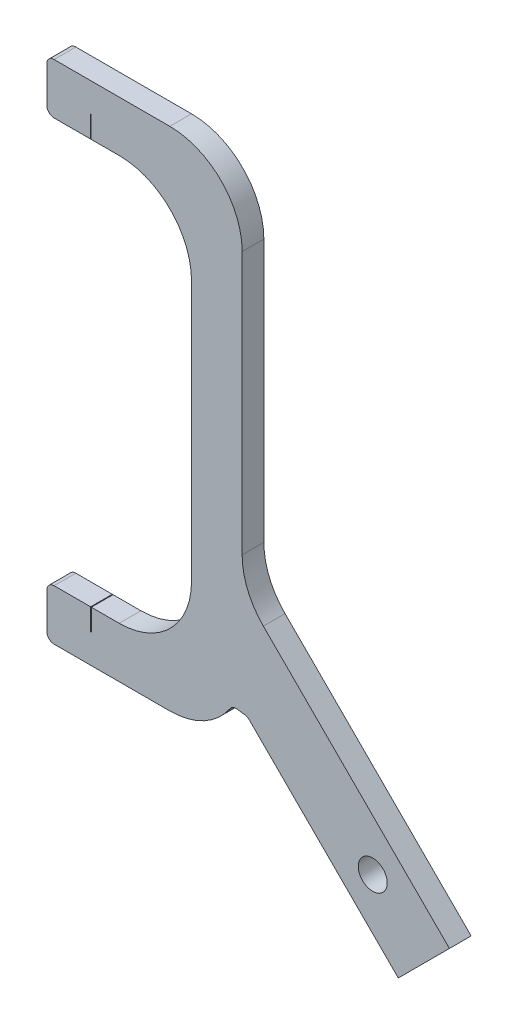
SolidWorks part; units mm, degrees
ref_plane "Front Plane" through (0, 0, 0) normal (0, 0, 1) x (1, 0, 0)
ref_plane "Top Plane" through (0, 0, 0) normal (0, 1, 0) x (1, 0, 0)
ref_plane "Right Plane" through (0, 0, 0) normal (1, 0, 0) x (0, 0, -1)
sketch "Sketch1" plane through (0, 0, 0) normal (0, 0, 1) x (1, 0, 0)
  line L0 (1, 0) -> (17, 0)
  line L1 (27, -10.0928) -> (27, -46.3053)
  line L2 (17, -70) -> (1, -70)
  line L3 (0, -69) -> (0, -64)
  line L4 (1, -63) -> (10, -63)
  line L5 (20, -53) -> (20, -17)
  line L6 (10, -7) -> (1, -7)
  line L7 (0, -6) -> (0, -1)
  line L14 (27, -10.0928) -> (27, -10)
  line L16 (25.3705, -46.8642) -> (52.661, -76.1084) construction
  line L18 (48.587, -86.1765) -> (27.9671, -65.5567)
  line L19 (48.587, -86.1765) -> (55.658, -79.1054)
  line L21 (55.658, -79.1054) -> (29.9289, -53.3763)
  line L22 (48.587, -86.1765) -> (33.8231, -52.1881) construction
  line L23 (27, -57.0782) -> (55.658, -79.1054) construction
  line L28 (26.2752, -65.1241) -> (27.3918, -65.2725)
  arc A1 (25.3122, -65.5594) -> (17, -70) centre (17, -60) cw
  arc A2 (10, -63) -> (20, -53) centre (10, -53) ccw
  arc A3 (20, -17) -> (10, -7) centre (10, -17) ccw
  arc A4 (0, -64) -> (1, -63) centre (1, -64) cw
  arc A5 (0, -69) -> (1, -70) centre (1, -69) ccw
  arc A6 (0, -1) -> (1, 0) centre (1, -1) cw
  arc A7 (0, -6) -> (1, -7) centre (1, -6) ccw
  arc A8 (17, 0) -> (27, -10) centre (17, -10) cw
  arc A9 (29.9289, -53.3763) -> (27, -46.3053) centre (37, -46.3053) cw
  arc A12 (27.3918, -65.2725) -> (27.9671, -65.5567) centre (27.26, -66.2638) cw
  arc A13 (26.2752, -65.1241) -> (25.3122, -65.5594) centre (26.1434, -66.1153) ccw
  point P10 (40.4318, -67.4022)
  point P11 (27, 0)
  point P14 (27, -70)
  point P25 (0, 0)
  point P30 (37.4955, 3.7564)
  dimension "D7" = 10
  dimension "D8" = 1
  dimension "D6" = 10
  dimension "D10" = 10
  dimension "D11" = 1
  dimension "D1" = 7
  dimension "D2" = 7
  dimension "D3" = 7
  dimension "D4" = 20
  dimension "D5" = 70
  dimension "D9" = 10
  dimension "D13" = 135
  dimension "D14" = 40
extrude "Boss-Extrude1" add sketch "Sketch1" along normal blind 3
sketch "Sketch2" plane through (0, -63, 0) normal (0, 1, 0) x (1, 0, 0)
  line L0 (27, -1.5) -> (6.1, -1.5) construction
  line L1 (27, -3) -> (27, 0) construction
  line L2 (10, 0) -> (1, 0) construction
  line L3 (6.05, -3) -> (6.15, -3)
  line L4 (6.05, -3) -> (6.05, 0)
  line L5 (6.05, 0) -> (6.15, 0)
  line L6 (6.15, -3) -> (6.15, 0)
  line L7 (6.05, -3) -> (6.15, 0) construction
  line L8 (6.05, 0) -> (6.15, -3) construction
  dimension "D2" = 0.1
extrude "Cut-Extrude1" cut sketch "Sketch2" against normal blind 3
sketch "Sketch3" plane through (0, -7, 0) normal (0, -1, 0) x (1, 0, 0)
  line L0 (27, 1.5) -> (6.05, 1.5) construction
  line L1 (27, 3) -> (27, 0) construction
  line L2 (1, 3) -> (10, 3) construction
  line L3 (6, 0) -> (6.1, 0)
  line L4 (6, 0) -> (6, 3)
  line L5 (6, 3) -> (6.1, 3)
  line L6 (6.1, 0) -> (6.1, 3)
  line L7 (6, 0) -> (6.1, 3) construction
  line L8 (6, 3) -> (6.1, 0) construction
  dimension "D2" = 0.1
extrude "Cut-Extrude2" cut sketch "Sketch3" against normal blind 3
sketch "Sketch4" plane through (0, 0, 3) normal (0, 0, 1) x (1, 0, 0)
  line L0 (52.1225, -82.641) -> (31.9288, -62.4473) construction
  line L2 (48.587, -86.1765) -> (55.658, -79.1054) construction
  circle A0 centre (45.0514, -75.5699) radius 2
  point P6 (0, 0)
  dimension "D1" = 4
  dimension "D2" = 10
extrude "Cut-Extrude3" cut sketch "Sketch4" against normal blind 10
equation "\"A.L\"= 0.07m"
equation "\"A.h\"= 0.007m"
equation "\"A.d\"= 0.003m"
equation "\"A.delta\"= 45.0001"
equation "\"A.w\"= 0.02m"
equation "\"A.v\"= 0.03m"
equation "\"A.s\"= 0.014m"
equation "\"A.t\"= 0.007m"
equation "\"B.L\"= 0.065m"
equation "\"B.h\"= 0.008m"
equation "\"B.s\"= 0.016m"
equation "\"B.t\"= 0.008m"
equation "\"C.h\"= 0.0065m"
equation "\"C.d\"= 0.003m"
equation "\"C.L\"= 0.05m"
equation "\"C.wmax\"= 0.005m"
equation "\"D.L\"= 0.06m"
equation "\"D.h\"= 0.008m"
equation "\"D.s\"= 0.012m"
equation "\"D.t\"= 0.008m"
equation "\"a_h\"= 0.0002m"
equation "\"a_d\"= 0.003m"
equation "\"a_L\"= 0.008m"
equation "\"b_h\"= 0.0004m"
equation "\"b_d\"= 0.003m"
equation "\"b_L\"= 0.007m"
equation "\"c_h\"= 0.0001m"
equation "\"c_d\"= 0.003m"
equation "\"c_L\"= 0.01m"
equation "\"d_h\"= 0.0001m"
equation "\"d_d\"= 0.003m"
equation "\"d_L\"= 0.01m"
equation "\"S.h\"= 0.015m"
equation "\"S.L\"= 0.09075m"
equation "\"D1@Sketch1\"=\"A.h\""
equation "\"D2@Sketch1\"=\"A.t\""
equation "\"D3@Sketch1\"=\"A.t\""
equation "\"D4@Sketch1\"=\"A.s\"+0.006"
equation "\"D5@Sketch1\"=\"A.L\""
equation "\"D1@Boss-Extrude1\"=\"A.d\""
equation "\"D1@Sketch2\"=\"A.h\"+\"A.s\"-\"a_h\"/2"
equation "\"D2@Sketch2\"=\"d_h\""
equation "\"D1@Sketch3\"=\"A.h\"+\"A.s\"-\"d_h\"/2"
equation "\"D2@Sketch3\"=\"d_h\""
